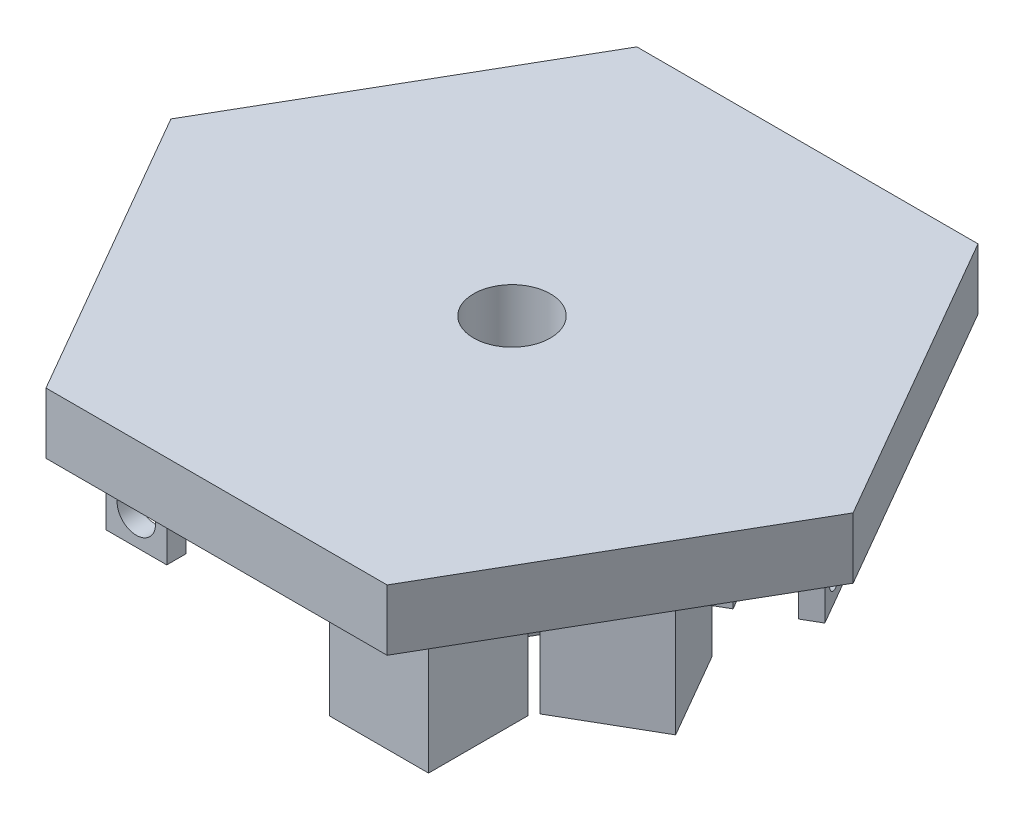
SolidWorks part; units mm, degrees
ref_plane "Front Plane" through (0, 0, 0) normal (0, 0, 1) x (1, 0, 0)
ref_plane "Top Plane" through (0, 0, 0) normal (0, 1, 0) x (1, 0, 0)
ref_plane "Right Plane" through (0, 0, 0) normal (1, 0, 0) x (0, 0, -1)
sketch "Sketch1" plane through (0, 0, 0) normal (0, 1, 0) x (1, 0, 0)
  line L1 (17.78, -30.7959) -> (35.56, 0)
  line L2 (35.56, 0) -> (17.78, 30.7959)
  line L3 (17.78, 30.7959) -> (-17.78, 30.7959)
  line L4 (-17.78, 30.7959) -> (-35.56, 0)
  line L5 (-35.56, 0) -> (-17.78, -30.7959)
  line L6 (-17.78, -30.7959) -> (17.78, -30.7959)
  circle A0 centre (0, 0) radius 30.7959 construction
  dimension "D1" = 35.56
extrude "Boss-Extrude1" add sketch "Sketch1" along normal blind 6.35 contours L4 L5 L6 L1 L2 L3
sketch "Sketch2" plane through (0, 0, 0) normal (0, -1, 0) x (1, 0, 0)
  line L0 (-5.175, 13.874) -> (-5.175, 3.524)
  line L5 (-3.175, 11.874) -> (3.175, 11.874)
  line L6 (-3.175, 11.874) -> (-3.175, 5.524)
  line L7 (-3.175, 5.524) -> (3.175, 5.524)
  line L8 (3.175, 11.874) -> (3.175, 5.524)
  line L9 (-3.175, 11.874) -> (3.175, 5.524) construction
  line L10 (-3.175, 5.524) -> (3.175, 11.874) construction
  line L11 (-5.175, 3.524) -> (-1.8925, 3.524)
  line L12 (5.175, 13.874) -> (5.175, 3.524)
  line L13 (-5.175, 13.874) -> (5.175, 13.874)
  line L14 (1.8925, 3.524) -> (5.175, 3.524)
  line L15 (-5.175, 3.524) -> (5.175, 3.524) construction
  line L16 (11.8707, -3.1874) -> (6.3714, -0.0124)
  line L17 (11.8707, -3.1874) -> (8.6957, -8.6866)
  line L18 (8.6957, -8.6866) -> (3.1964, -5.5116)
  line L19 (6.3714, -0.0124) -> (3.1964, -5.5116)
  line L20 (2.1056, -3.4009) -> (0.4644, -6.2437)
  line L21 (9.4277, -11.4187) -> (0.4644, -6.2437)
  line L22 (14.6027, -2.4553) -> (9.4277, -11.4187)
  line L23 (14.6027, -2.4553) -> (5.6394, 2.7197)
  line L24 (5.6394, 2.7197) -> (3.9981, -0.1231)
  line L25 (-8.6957, -8.6866) -> (-3.1964, -5.5116)
  line L26 (-8.6957, -8.6866) -> (-11.8707, -3.1874)
  line L27 (-11.8707, -3.1874) -> (-6.3714, -0.0124)
  line L28 (-3.1964, -5.5116) -> (-6.3714, -0.0124)
  line L29 (-3.9981, -0.1231) -> (-5.6394, 2.7197)
  line L30 (-14.6027, -2.4553) -> (-5.6394, 2.7197)
  line L31 (-9.4277, -11.4187) -> (-14.6027, -2.4553)
  line L32 (-9.4277, -11.4187) -> (-0.4644, -6.2437)
  line L33 (-0.4644, -6.2437) -> (-2.1056, -3.4009)
  circle A0 centre (0, 0) radius 4 construction
  arc A2 (-1.8925, 3.524) -> (1.8925, 3.524) centre (0, 0) cw
  arc A3 (3.9981, -0.1231) -> (2.1056, -3.4009) centre (0, 0) cw
  arc A4 (-2.1056, -3.4009) -> (-3.9981, -0.1231) centre (0, 0) cw
  point P3 (0, 8.699)
  point P37 (0, 0)
  dimension "D1" = 8
  dimension "D3" = 1.524
  dimension "D4" = 2
  dimension "D2" = 6.35
  dimension "D5" = 3
sketch "Sketch6" plane through (0, 6.35, 0) normal (0, 1, 0) x (1, 0, 0)
  circle A0 centre (0, 0) radius 4
  dimension "D1" = 8
extrude "Cut-Extrude1" cut sketch "Sketch6" against normal through all
extrude "Boss-Extrude2" add sketch "Sketch2" along normal blind 25.4
sketch "Sketch7" plane through (0, 0, 0) normal (0, -1, 0) x (1, 0, 0)
  line L0 (-14.5653, 20.7726) -> (-8.2153, 20.7726)
  line L1 (-8.2153, 20.7726) -> (-8.2153, 18.7726)
  line L2 (-8.2153, 18.7726) -> (-14.5653, 18.7726)
  line L3 (-14.5653, 18.7726) -> (-14.5653, 20.7726)
  line L5 (-17.78, 30.7959) -> (17.78, 30.7959) construction
  line L7 (-14.5653, 25.7726) -> (-14.5653, 27.7726)
  line L8 (-14.5653, 27.7726) -> (-8.2153, 27.7726)
  line L9 (-8.2153, 27.7726) -> (-8.2153, 25.7726)
  line L10 (-8.2153, 25.7726) -> (-14.5653, 25.7726)
  line L11 (-5.175, 13.874) -> (-5.175, 3.524) construction
  line L12 (25.2722, 2.2276) -> (22.0972, -3.2716)
  line L13 (22.0972, -3.2716) -> (20.3652, -2.2716)
  line L14 (20.3652, -2.2716) -> (23.5402, 3.2276)
  line L15 (23.5402, 3.2276) -> (25.2722, 2.2276)
  line L16 (29.6024, -0.2724) -> (31.3344, -1.2724)
  line L17 (31.3344, -1.2724) -> (28.1594, -6.7716)
  line L18 (28.1594, -6.7716) -> (26.4274, -5.7716)
  line L19 (26.4274, -5.7716) -> (29.6024, -0.2724)
  line L20 (-10.7069, -23.0002) -> (-13.8819, -17.501)
  line L21 (-13.8819, -17.501) -> (-12.1499, -16.501)
  line L22 (-12.1499, -16.501) -> (-8.9749, -22.0002)
  line L23 (-8.9749, -22.0002) -> (-10.7069, -23.0002)
  line L24 (-15.0371, -25.5002) -> (-16.7691, -26.5002)
  line L25 (-16.7691, -26.5002) -> (-19.9441, -21.001)
  line L26 (-19.9441, -21.001) -> (-18.2121, -20.001)
  line L27 (-18.2121, -20.001) -> (-15.0371, -25.5002)
  line L28 (-17.78, -30.7959) -> (-35.56, 0) construction
  line L29 (35.56, 0) -> (17.78, -30.7959) construction
  point P13 (-11.3903, 18.7726)
  dimension "D1" = 20.7726
  dimension "D2" = 2
  dimension "D4" = 5
  dimension "D5" = 6.2153
  dimension "D6" = 6.35
  dimension "D8" = 3.0233
  dimension "D9" = 3.0233
  dimension "D3" = 2
  dimension "D7" = 3
extrude "Boss-Extrude3" add sketch "Sketch7" along normal blind 6.35
sketch "Sketch9" plane through (0, 0, 27.7726) normal (0, 0, 1) x (1, 0, 0)
  line L0 (-8.2153, -6.35) -> (-14.5653, -6.35) construction
  line L1 (-17.78, 0) -> (17.78, 0) construction
  circle A0 centre (-11.3903, -3.2626) radius 2
  point P4 (-11.3903, -6.35)
  dimension "D1" = 4
  dimension "D2" = 3.2626
extrude "Cut-Extrude2" cut sketch "Sketch9" against normal blind 9.588
pattern_circular "CirPattern1" count 3 over 360 about axis through (0, 0, 0) along (0, 1, 0) of "Cut-Extrude2" reverse direction yes
